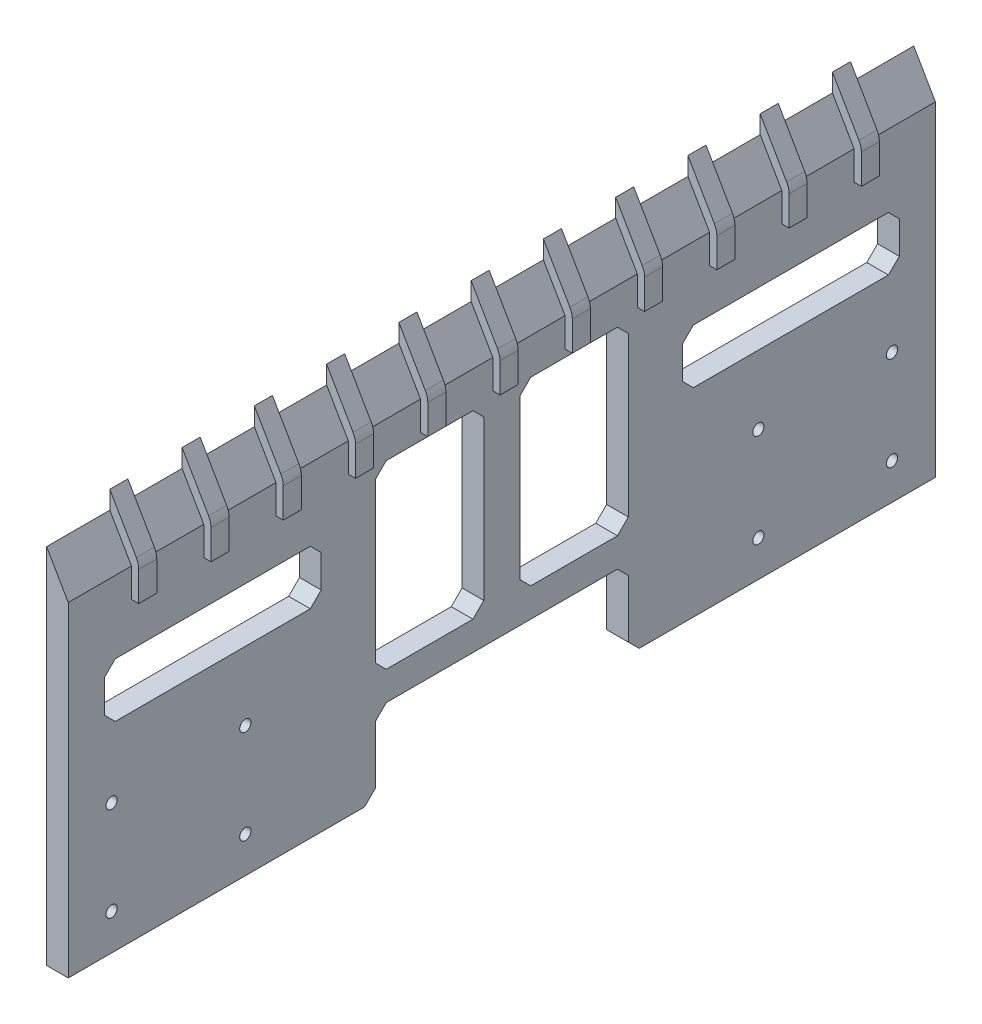
SolidWorks part; units mm, degrees
ref_plane "前视基准面" through (0, 0, 0) normal (0, 0, 1) x (1, 0, 0)
ref_plane "上视基准面" through (0, 0, 0) normal (0, 1, 0) x (1, 0, 0)
ref_plane "右视基准面" through (0, 0, 0) normal (1, 0, 0) x (0, 0, -1)
sketch "草图1" plane through (0, 0, 0) normal (1, 0, 0) x (0, 0, -1)
  line L1 (0, 0) -> (240, 0)
  line L2 (0, 0) -> (0, -90)
  line L3 (0, -90) -> (240, -90)
  line L4 (240, 0) -> (240, -90)
  dimension "D1" = 240
  dimension "D2" = 90
extrude "凸台-拉伸1" add sketch "草图1" along normal blind 6
sketch "草图2" plane through (6, 0, 0) normal (1, 0, 0) x (0, 0, -1)
  line L0 (0, 0) -> (0, -90) construction
  line L1 (12, -54) -> (49, -54) construction
  line L2 (12, -54) -> (12, -80) construction
  line L3 (12, -80) -> (49, -80) construction
  line L4 (49, -54) -> (49, -80) construction
  line L5 (240, 0) -> (0, 0) construction
  line L6 (120, 0) -> (120, -90) construction
  line L7 (0, -90) -> (240, -90) construction
  line L8 (191, -54) -> (191, -80) construction
  line L9 (228, -80) -> (191, -80) construction
  line L10 (228, -54) -> (228, -80) construction
  line L11 (228, -54) -> (191, -54) construction
  circle A0 centre (12, -54) radius 1.55
  circle A1 centre (49, -80) radius 1.55
  circle A2 centre (49, -54) radius 1.55
  circle A3 centre (12, -80) radius 1.55
  circle A4 centre (228, -80) radius 1.55
  circle A5 centre (191, -54) radius 1.55
  circle A6 centre (191, -80) radius 1.55
  circle A7 centre (228, -54) radius 1.55
  dimension "D5" = 3.1
  dimension "D1" = 12
  dimension "D2" = 54
  dimension "D3" = 37
  dimension "D4" = 26
extrude "切除-拉伸1" cut sketch "草图2" against normal through all
sketch "草图3" plane through (6, 0, 0) normal (1, 0, 0) x (0, 0, -1)
  line L0 (120, 0) -> (120, -90) construction
  line L1 (10, -20) -> (70, -20)
  line L2 (10, -20) -> (10, -35)
  line L3 (10, -35) -> (70, -35)
  line L4 (70, -20) -> (70, -35)
  line L5 (240, 0) -> (0, 0) construction
  line L6 (0, -90) -> (240, -90) construction
  line L7 (0, 0) -> (0, -90) construction
  line L8 (170, -20) -> (170, -35)
  line L9 (230, -35) -> (170, -35)
  line L10 (230, -20) -> (230, -35)
  line L11 (230, -20) -> (170, -20)
  dimension "D1" = 10
  dimension "D2" = 20
  dimension "D3" = 15
  dimension "D4" = 60
extrude "切除-拉伸2" cut sketch "草图3" against normal through all
sketch "草图4" plane through (6, 0, 0) normal (1, 0, 0) x (0, 0, -1)
  line L0 (120, 0) -> (120, -90) construction
  line L1 (85, -10) -> (115, -10)
  line L2 (85, -10) -> (85, -60)
  line L3 (85, -60) -> (115, -60)
  line L4 (115, -10) -> (115, -60)
  line L5 (240, 0) -> (0, 0) construction
  line L6 (0, -90) -> (240, -90) construction
  line L7 (0, 0) -> (0, -90) construction
  line L8 (125, -10) -> (125, -60)
  line L9 (155, -60) -> (125, -60)
  line L10 (155, -10) -> (155, -60)
  line L11 (155, -10) -> (125, -10)
  dimension "D1" = 10
  dimension "D2" = 50
  dimension "D3" = 85
  dimension "D4" = 30
extrude "切除-拉伸3" cut sketch "草图4" against normal through all contours L4 L1 L2 L3 | L8 L9 L10 L11 region at (6, -35, -100)
sketch "草图8" plane through (6, 0, 0) normal (1, 0, 0) x (0, 0, -1)
  line L0 (0, -90) -> (240, -90) construction
  line L1 (85, -68) -> (155, -68)
  line L2 (85, -68) -> (85, -90)
  line L3 (85, -90) -> (155, -90)
  line L4 (155, -68) -> (155, -90)
  line L5 (155, -60) -> (125, -60) construction
  dimension "D1" = 70
  dimension "D2" = 22
  dimension "D3" = 8
extrude "切除-拉伸5" cut sketch "草图8" against normal through all
sketch "草图5" plane through (0, 0, 0) normal (-1, 0, 0) x (0, 0, 1)
  circle A0 centre (-191, -80) radius 3
  circle A1 centre (-228, -80) radius 3
  circle A2 centre (-191, -54) radius 3
  circle A3 centre (-228, -54) radius 3
  circle A4 centre (-45, -80) radius 3
  circle A5 centre (-12, -80) radius 3
  circle A6 centre (-12, -54) radius 3
  circle A7 centre (-49, -54) radius 3
  dimension "D1" = 6
extrude "切除-拉伸4" cut sketch "草图5" against normal blind 3
sketch "草图6" plane through (0, 0, 0) normal (0, 0, 1) x (1, 0, 0)
  line L0 (6, 0) -> (0, 0)
  line L1 (0, 0) -> (0, 10.3923)
  line L2 (0, 10.3923) -> (6, 0)
  dimension "D1" = 30
extrude "凸台-拉伸2" add sketch "草图6" against normal blind 240
ref_plane "基准面1" through (0, 0, -117.5) normal (0, 0, 1) x (1, 0, 0)
sketch "草图7" plane through (0, 0, -117.5) normal (0, 0, 1) x (1, 0, 0)
  line L0 (0, 10.3923) -> (0, 15.3923)
  line L1 (0, 15.3923) -> (8, 1.5359)
  line L2 (8, 1.5359) -> (8, -8)
  line L3 (8, -8) -> (6, -8)
  line L4 (6, 0) -> (6, -90) construction
  line L5 (6, -8) -> (6, 0)
  line L6 (6, 0) -> (0, 10.3923)
  dimension "D1" = 5
  dimension "D2" = 2
  dimension "D3" = 8
extrude "凸台-拉伸3" add sketch "草图7" against normal blind 5
pattern_linear "阵列(线性)5" count 6 spacing 20 along (0, 0, 1) count 6 spacing 20 along (0, 0, -1) of "凸台-拉伸3"
fillet "圆角5" radius 5 11 edges at (8, 1.5359, -20) (8, 1.5359, -40) (8, 1.5359, -60) (8, 1.5359, -80) (8, 1.5359, -100) (8, 1.5359, -120) (8, 1.5359, -140) (8, 1.5359, -160) (8, 1.5359, -180) (8, 1.5359, -200) (8, 1.5359, -220)
chamfer "倒角1" distance 3 angle 45 20 edges at (3, -60, -85) (3, -60, -125) (3, -35, -170) (3, -35, -230) (3, -60, -155) (3, -60, -115) (3, -20, -230) (3, -10, -155) (3, -10, -115) (3, -20, -170) (3, -10, -125) (3, -10, -85) (3, -35, -70) (3, -20, -70) (3, -35, -10) (3, -20, -10) (3, -68, -155) (3, -68, -85) (3, -90, -155) (3, -90, -85)
